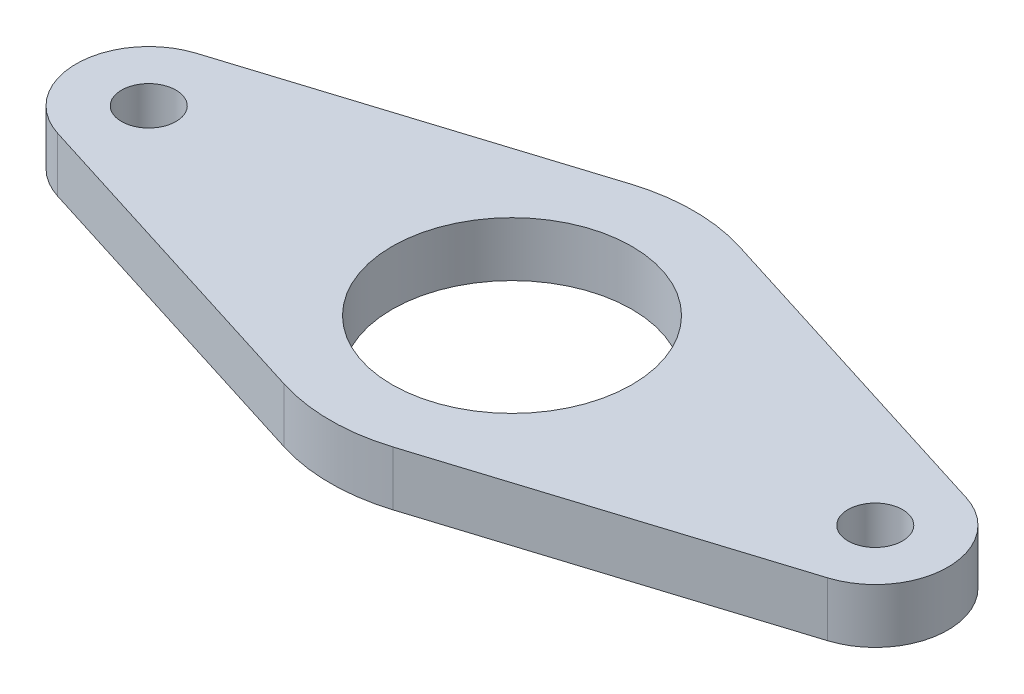
SolidWorks part; units mm, degrees
material "碳纤维"
ref_plane "前视基准面" through (0, 0, 0) normal (0, 0, 1) x (1, 0, 0)
ref_plane "上视基准面" through (0, 0, 0) normal (0, 1, 0) x (1, 0, 0)
ref_plane "右视基准面" through (0, 0, 0) normal (1, 0, 0) x (0, 0, -1)
sketch "草图1" plane through (0, 0, 0) normal (0, 1, 0) x (1, 0, 0)
  line L0 (21.2, 3.8158) -> (3, 9.5394)
  line L1 (20, 0) -> (0, 0) construction
  line L2 (0, 0) -> (0, 10) construction
  line L3 (21.2, -3.8158) -> (3, -9.5394)
  line L4 (-21.2, -3.8158) -> (-3, -9.5394)
  line L5 (-21.2, 3.8158) -> (-3, 9.5394)
  arc A0 (3, 9.5394) -> (-3, 9.5394) centre (0, 0) ccw
  arc A1 (21.2, -3.8158) -> (21.2, 3.8158) centre (20, 0) ccw
  arc A2 (-21.2, -3.8158) -> (-21.2, 3.8158) centre (-20, 0) cw
  arc A3 (-3, -9.5394) -> (3, -9.5394) centre (0, 0) ccw
  circle A4 centre (0, 0) radius 6.6
  circle A5 centre (20, 0) radius 1.5
  circle A6 centre (-20, 0) radius 1.5
  point P27 (0, 0)
  dimension "D1" = 3
  dimension "D2" = 13.2
  dimension "D3" = 10
  dimension "D4" = 4
  dimension "D5" = 40
extrude "凸台-拉伸1" add sketch "草图1" along normal blind 3 contours L4 A3 L3 A1 L0 A0 L5 A2 A4 A6 A5 region at (23.48, 0, 0)
ref_axis "基准轴1" through (0, 242.0132, 0) along (0, -1, 0)
move or copy body "实体-移动/复制1" [suppressed] bodies to move or copy 106
